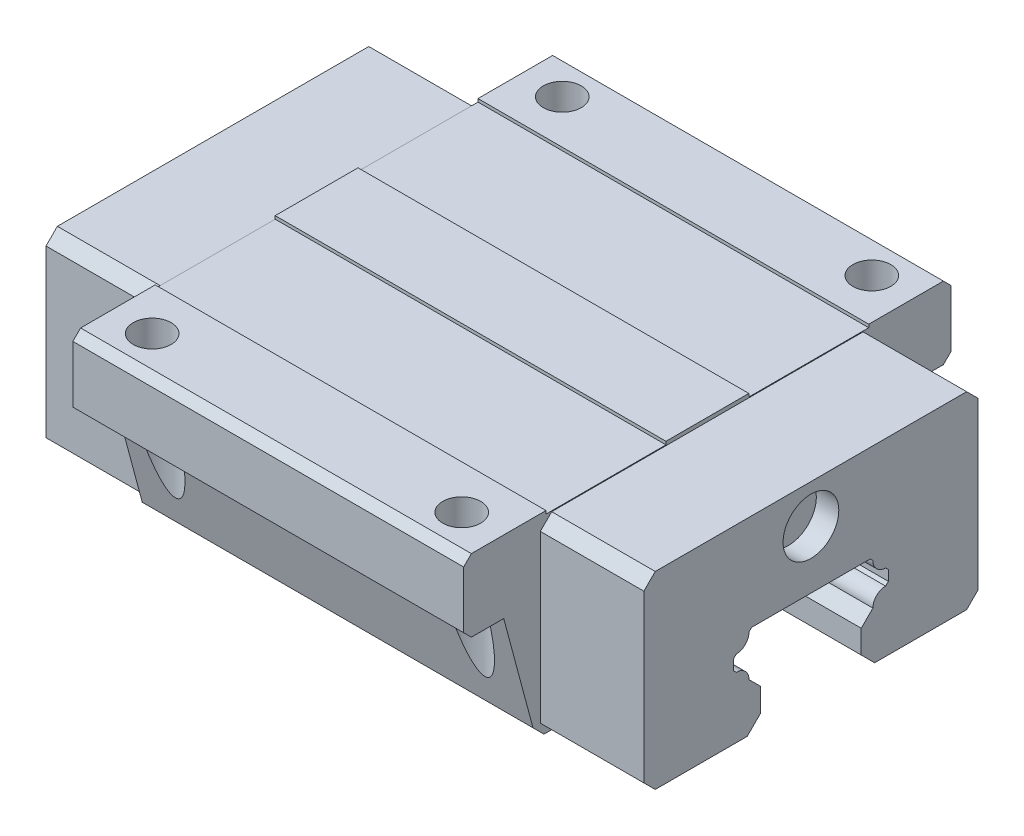
SolidWorks part; units mm, degrees
material "1060 Alloy"
ref_plane "Front Plane" through (0, 0, 0) normal (0, 0, 1) x (1, 0, 0)
ref_plane "Top Plane" through (0, 0, 0) normal (0, 1, 0) x (1, 0, 0)
ref_plane "Right Plane" through (0, 0, 0) normal (1, 0, 0) x (0, 0, -1)
sketch "Sketch2" plane through (0, 0, 0) normal (1, 0, 0) x (0, 0, -1)
  line L0 (0, 22.5899) -> (0, 0.5499) construction
  line L1 (-9.6464, -1.0186) -> (-9.6464, -2.6614) construction
  line L2 (-9.6464, -2.6614) -> (-8.0036, -2.6614) construction
  line L3 (-10, 0) -> (0, 0) construction
  line L4 (20.2658, -14.5) -> (-12.926, -14.5) construction
  line L8 (-8.235, -8.9) -> (-20.12, -8.9)
  line L9 (-20.12, -8.9) -> (-21.59, -7.43)
  line L10 (-21.59, -7.43) -> (-21.59, 14.03)
  line L11 (-21.59, 14.03) -> (-20.12, 15.5)
  line L12 (-20.12, 15.5) -> (0, 15.5)
  line L13 (-20.12, 15.5) -> (-20.12, -8.9) construction
  line L14 (0, 15.5) -> (0, 3.015)
  line L17 (-6.5, -7.165) -> (-8.235, -8.9)
  line L18 (-6.5, -4.165) -> (-6.5, -7.165)
  line L19 (-8.0036, -2.6614) -> (-6.5, -4.165)
  line L20 (-10, -0.665) -> (-9.6464, -1.0186)
  line L21 (-10, 0.665) -> (-10, -0.665)
  line L22 (-9.6464, 1.0186) -> (-10, 0.665)
  line L23 (-7.65, 3.015) -> (-8.0036, 2.6614)
  line L24 (0, 3.015) -> (-7.65, 3.015)
  line L25 (-8.0036, 2.6614) -> (-9.6464, 1.0186) construction
  line L26 (-9.6464, -1.0186) -> (-8.0036, -2.6614) construction
  line L27 (-8.0036, 2.6614) -> (-9.6464, 2.6614) construction
  line L28 (-9.6464, 2.6614) -> (-9.6464, 1.0186) construction
  arc A2 (-8.0036, -2.6614) -> (-9.6464, -1.0186) centre (-9.6464, -2.6614) ccw
  arc A3 (-9.6464, 1.0186) -> (-8.0036, 2.6614) centre (-9.6464, 2.6614) ccw
  point P4 (-10, 0)
  point P5 (-23.309, 31.262)
  point P26 (0, 2.6696)
  dimension "D2" = 0.5
  dimension "D3" = 10
  dimension "D4" = 45
  dimension "D5" = 1.33
  dimension "D6" = 30
  dimension "D7" = 7.65
  dimension "D8" = 3
  dimension "D9" = 21.59
  dimension "D10" = 1.47
  dimension "D11" = 21.46
  dimension "D12" = 45
  dimension "D13" = 6.5
  dimension "D14" = 24.4
  dimension "D15" = 14.5
extrude "Boss-Extrude1" add sketch "Sketch2" along normal blind 38.63
sketch "Sketch3" plane through (0, 0, 0) normal (1, 0, 0) x (0, 0, -1)
  line L0 (-20.12, -8.9) -> (-21.12, -8.9)
  line L1 (-21.12, -8.9) -> (-22.5342, -7.4858)
  line L2 (-22.5342, -7.4858) -> (-26.3203, 6.6442)
  line L3 (-26.3203, 6.6442) -> (-31.5, 6.6442)
  line L4 (-31.5, 6.6442) -> (-31.5, 16)
  line L5 (-31.5, 16) -> (-20.855, 16)
  line L6 (-20.855, 16) -> (-20.855, 15.6)
  line L7 (-20.855, 15.6) -> (-5.355, 15.6)
  line L8 (-5.355, 15.6) -> (-5.355, 16)
  line L9 (-5.355, 16) -> (0, 16)
  line L10 (0, 16) -> (0, 15.5)
  line L11 (0, 15.5) -> (-20.12, 15.5)
  line L12 (-20.12, 15.5) -> (-21.59, 14.03)
  line L13 (-21.59, 14.03) -> (-21.59, -7.43)
  line L14 (-21.59, -7.43) -> (-20.12, -8.9)
  line L15 (-22.5342, -7.4858) -> (-30.0907, -7.4858) construction
  line L16 (-20.855, 15.6) -> (-20.855, 14.765) construction
  line L17 (-20.855, 16) -> (-5.355, 16) construction
  line L18 (0, 3.015) -> (0, 15.5) construction
  dimension "D1" = 1
  dimension "D2" = 45
  dimension "D3" = 2
  dimension "D4" = 75
  dimension "D5" = 14.13
  dimension "D6" = 31.5
  dimension "D7" = 0.5
  dimension "D8" = 0.1
  dimension "D9" = 15.5
extrude "Boss-Extrude2" add sketch "Sketch3" along normal offset from surface (25.25 mm away) 13.38 up to face at (38.63, 0.9063, 10.4328)
chamfer "Chamfer1" distance 1 angle 45 2 edges at (12.625, 6.6442, 31.5) (12.625, 16, 31.5)
sketch "Sketch4" plane through (0, 16, 0) normal (0, 1, 0) x (1, 0, 0)
  line L0 (20, -26.5) -> (25.25, -26.5) construction
  line L1 (25.25, -20.855) -> (25.25, -30.5) construction
  line L2 (20, -26.5) -> (20, -31.5) construction
  line L3 (25.25, -31.5) -> (0, -31.5) construction
  line L4 (25.25, 0) -> (0, 0) construction
  circle A0 centre (20, -26.5) radius 2.45
  dimension "D1" = 4.9
  dimension "D2" = 26.5
  dimension "D3" = 5.25
extrude "Cut-Extrude1" cut sketch "Sketch4" against normal through all
sketch "Sketch5" plane through (0, 16, 0) normal (0, 1, 0) x (1, 0, 0)
  circle A0 centre (20, -26.5) radius 3
  dimension "D1" = 6
extrude "Cut-Extrude2" cut sketch "Sketch5" against normal through all from offset 8.5 offset against normal yes
mirror "Mirror1" about plane through (0, 0, 0) normal (0, 0, 1) of bodies 104 110
sketch "Sketch12" plane through (38.63, 0, 0) normal (1, 0, 0) x (0, 0, -1)
  line L0 (0, 10.5) -> (0, 0) construction
  line L1 (-20.12, 15.5) -> (20.12, 15.5) construction
  circle A0 centre (0, 10.5) radius 3.6
  dimension "D1" = 7.2
  dimension "D2" = 5
extrude "Cut-Extrude8" cut sketch "Sketch12" against normal blind 2.9
mirror "Mirror2" about plane through (0, 0, 0) normal (1, 0, 0) of bodies 112 113
